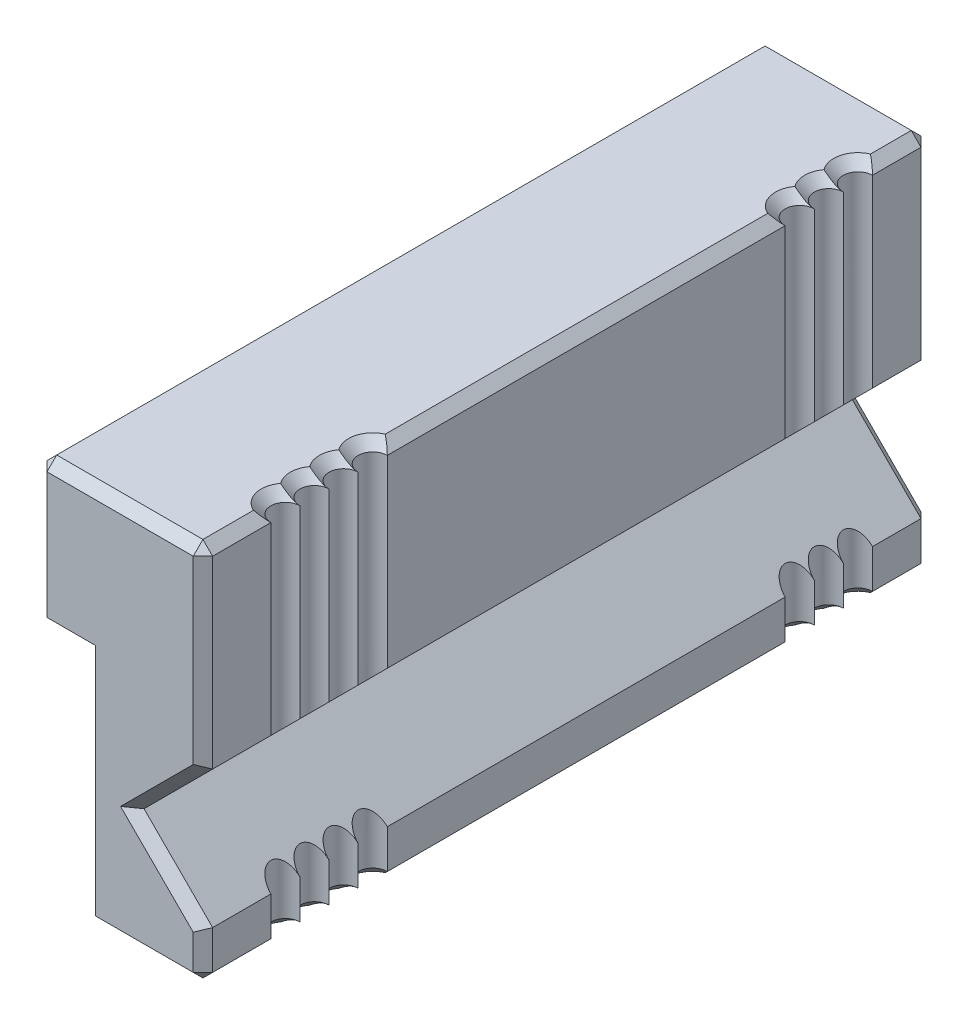
SolidWorks part; units mm, degrees
ref_plane "Front Plane" through (0, 0, 0) normal (0, 0, 1) x (1, 0, 0)
ref_plane "Top Plane" through (0, 0, 0) normal (0, 1, 0) x (1, 0, 0)
ref_plane "Right Plane" through (0, 0, 0) normal (1, 0, 0) x (0, 0, -1)
sketch "Sketch1" plane through (0, 0, 0) normal (0, 0, 1) x (1, 0, 0)
  line L0 (-7.0711, 0) -> (0, 7.0711)
  line L1 (0, 7.0711) -> (0, 27.0711)
  line L2 (0, 27.0711) -> (-17.0711, 27.0711)
  line L3 (-17.0711, 27.0711) -> (-17.0711, 12.0711)
  line L4 (-17.0711, 12.0711) -> (-12.0711, 12.0711)
  line L5 (-12.0711, 12.0711) -> (-12.0711, -12.0711)
  line L6 (-12.0711, -12.0711) -> (0, -12.0711)
  line L7 (0, -12.0711) -> (0, -7.0711)
  line L8 (0, -7.0711) -> (-7.0711, 0)
  circle A0 centre (0, 0) radius 5 construction
  dimension "D1" = 10
  dimension "D2" = 0
  dimension "D3" = 5
  dimension "D4" = 15
  dimension "D5" = 5
  dimension "D6" = 5
  dimension "D7" = 20
extrude "Boss-Extrude1" add sketch "Sketch1" along normal blind 75
sketch "Sketch2" plane through (0, 27.0711, 0) normal (0, 1, 0) x (1, 0, 0)
  circle A0 centre (0, -7.5) radius 1.5
  dimension "D1" = 3
  dimension "D2" = 6
extrude "Cut-Extrude1" cut sketch "Sketch2" against normal through all
pattern_linear "LPattern2" count 22 spacing 3 along (0, 0, 1) skipping (3, 0), (4, 0), (5, 0), (6, 0), (7, 0), (8, 0), (9, 0), (10, 0), (11, 0), (12, 0), (13, 0), (14, 0), (15, 0), (16, 0), (17, 0), (18, 0), (19, 0), (20, 0), (21, 0) of "Cut-Extrude1"
sketch "Sketch3" plane through (0, 27.0711, 0) normal (0, 1, 0) x (1, 0, 0)
  line L0 (0, -75) -> (0, -15) construction
  arc A0 (0, -12) -> (0, -15) centre (0, -13.5) ccw construction
  arc A1 (0, -12) -> (0, -15) centre (0, -13.5) ccw
  circle A2 centre (0, -57.5) radius 1.5
  line M2 (0, -75) -> (0, -15)
  dimension "D1" = 3
  dimension "D2" = 44
extrude "Cut-Extrude2" cut sketch "Sketch3" against normal through all contours A2 M2 region at (-0.6366, 27.0711, 57.5)
pattern_linear "LPattern3" count 4 spacing 3 along (0, 0, 1) of "Cut-Extrude2"
chamfer "Chamfer2" distance 1 angle 45 41 edges at (0, 27.0711, 71.5) (-1.5, 27.0711, 13.5) (-1.5, 27.0711, 10.5) (-1.5, 27.0711, 7.5) (0, 27.0711, 3) (-1.5, -12.0711, 13.5) (-1.5, -12.0711, 10.5) (-1.5, -12.0711, 7.5) (0, -12.0711, 3) (0, -12.0711, 71.5) (0, -9.5711, 75) (-6.0355, -12.0711, 75) (-14.5711, 12.0711, 75) (-3.5355, -3.5355, 75) (-3.5355, 3.5355, 75) (0, 17.0711, 75) (-8.5355, 27.0711, 75) (-3.5355, 3.5355, 0) (0, 17.0711, 0) (-8.5355, 27.0711, 0) (-17.0711, 27.0711, 37.5) (-17.0711, 19.5711, 75) (-17.0711, 12.0711, 37.5) (-17.0711, 19.5711, 0) (-14.5711, 12.0711, 0) (-3.5355, -3.5355, 0) (0, -9.5711, 0) (-6.0355, -12.0711, 0) (-12.0711, 0, 75) (-12.0711, -12.0711, 37.5) (-12.0711, 0, 0) (0, 27.0711, 35.5) (0, -12.0711, 35.5) (-1.5, 27.0711, 66.5) (-1.5, 27.0711, 63.5) (-1.5, 27.0711, 60.5) (-1.5, 27.0711, 57.5) (-1.5, -12.0711, 57.5) (-1.5, -12.0711, 60.5) (-1.5, -12.0711, 63.5) (-1.5, -12.0711, 66.5)
equation "\"Drill Bit OD\"=3"
equation "\"Shaft OD\"=10"
equation "\"Number of Holes\"= 11"
equation "\"Face Gap\"= 0"
equation "\"Shaft OD Oversize\"= 0.4"
equation "\"Drill Bit Hole Oversize\"= 0.4"
equation "\"D1@Sketch1\"=\"Shaft OD\""
equation "\"D2@Sketch1\"=\"Face Gap\" / 2"
equation "\"D1@Boss-Extrude1\"=(\"Number of Holes\" + 1.5) * \"Drill Bit OD\" * 2"
equation "\"D1@Sketch2\"=\"Drill Bit OD\""
equation "\"D3@LPattern2\"=\"Drill Bit OD\""
equation "\"D1@LPattern2\"=\"Number of Holes\"*2"
equation "\"D2@Sketch2\"=\"Drill Bit OD\"*2"
equation "\"D1@Sketch3\"=\"Drill Bit OD\""
equation "\"D3@LPattern3\"=\"Drill Bit OD\""
